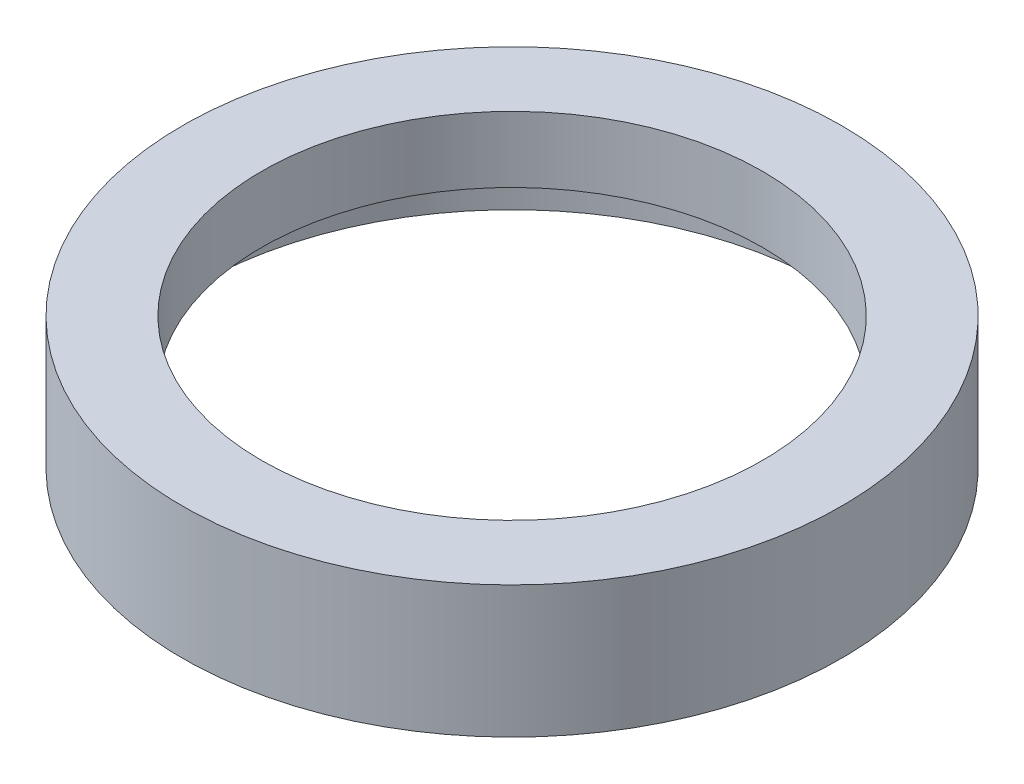
SolidWorks part; units mm, degrees
material "AISI 316 Annealed Stainless Steel Bar (SS)"
ref_plane "Front Plane" through (0, 0, 0) normal (0, 0, 1) x (1, 0, 0)
ref_plane "Top Plane" through (0, 0, 0) normal (0, 1, 0) x (1, 0, 0)
ref_plane "Right Plane" through (0, 0, 0) normal (1, 0, 0) x (0, 0, -1)
sketch "Sketch1" plane through (0, 0, 0) normal (0, 0, 1) x (1, 0, 0)
  line L0 (-158.75, 0) -> (-158.75, 63.5)
  line L1 (-158.75, 63.5) -> (-120.65, 63.5)
  line L2 (-120.65, 63.5) -> (-120.65, 31.75)
  line L3 (-120.65, 31.75) -> (-127, 31.75)
  line L4 (-127, 31.75) -> (-127, 57.15)
  line L5 (-127, 57.15) -> (-152.4, 57.15)
  line L6 (-152.4, 57.15) -> (-152.4, 0)
  line L7 (-152.4, 0) -> (-158.75, 0)
  line L8 (0, 0) -> (0, 71.9152) construction
  point P11 (-139.7, 63.5)
  dimension "D1" = 152.4
  dimension "D2" = 63.5
  dimension "D3" = 6.35
  dimension "D4" = 6.35
  dimension "D5" = 6.35
  dimension "D6" = 25.4
  dimension "D7" = 25.4
revolve "Revolve1" add sketch "Sketch1" angle 360 about L8
